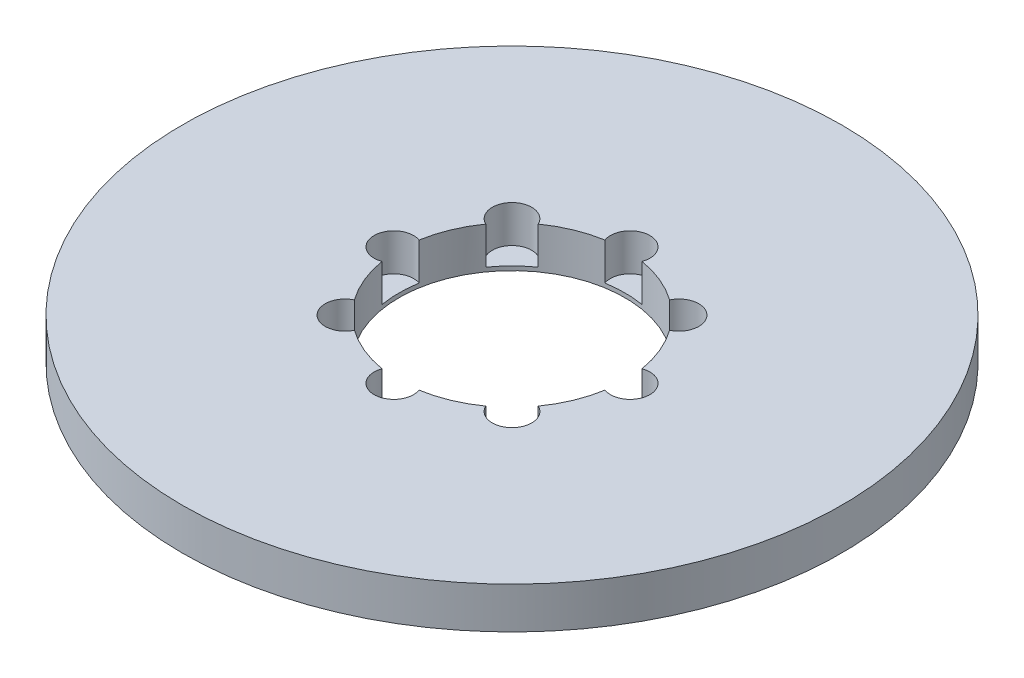
SolidWorks part; units mm, degrees
ref_plane "Front Plane" through (0, 0, 0) normal (0, 0, 1) x (1, 0, 0)
ref_plane "Top Plane" through (0, 0, 0) normal (0, 1, 0) x (1, 0, 0)
ref_plane "Right Plane" through (0, 0, 0) normal (1, 0, 0) x (0, 0, -1)
sketch "Sketch1" plane through (0, 0, 0) normal (0, 1, 0) x (1, 0, 0)
  circle A0 centre (0, 0) radius 87.5
  dimension "FLANGE_OD" = 175
extrude "Boss-Extrude1" add sketch "Sketch1" along normal blind 11
sketch "Sketch2" plane through (0, 0, 0) normal (0, 1, 0) x (1, 0, 0)
  circle A0 centre (0, 0) radius 30
  dimension "BORE_D" = 60
extrude "Cut-Extrude1" cut sketch "Sketch2" along normal through all
sketch "Sketch3" plane through (0, 11, 0) normal (0, 1, 0) x (1, 0, 0)
  circle A0 centre (0, 0) radius 31.3651 construction
  circle A1 centre (-31.3651, 0) radius 5.237
  dimension "BOLT_D" = 10.474
  dimension "BOLT_PCD" = 62.7301
extrude "Cut-Extrude2" cut sketch "Sketch3" against normal blind 9.8933
pattern_circular "CirPattern1" count 8 over 360 about axis through (0, 0, 0) along (0, 1, 0) of "Cut-Extrude2"
